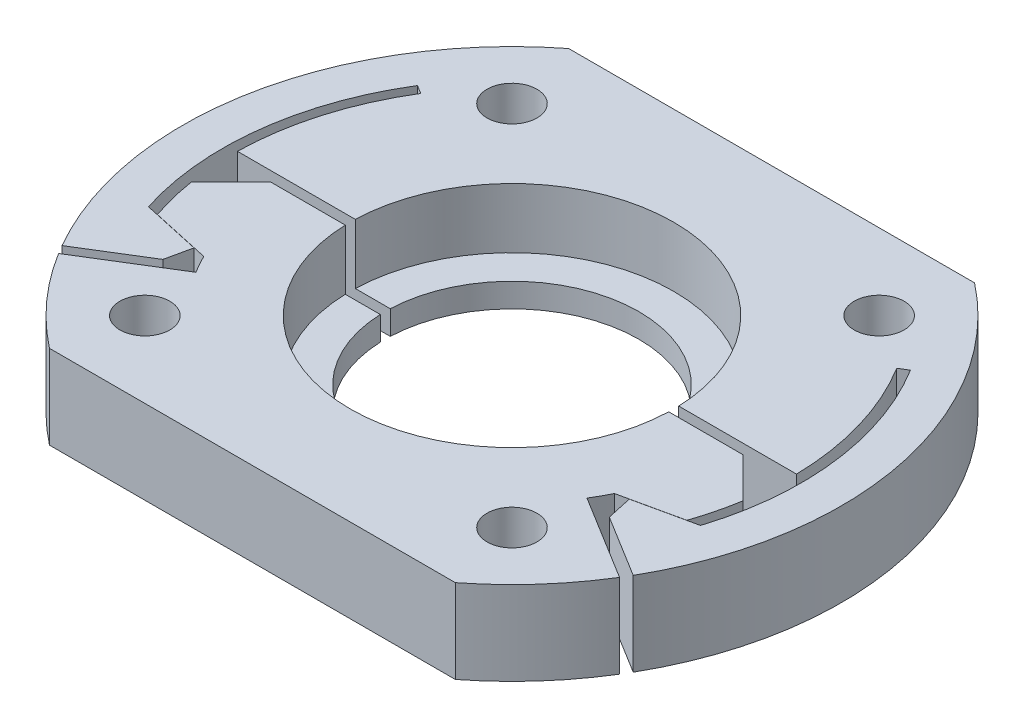
SolidWorks part; units mm, degrees
ref_plane "Front Plane" through (0, 0, 0) normal (0, 0, 1) x (1, 0, 0)
ref_plane "Top Plane" through (0, 0, 0) normal (0, 1, 0) x (1, 0, 0)
ref_plane "Right Plane" through (0, 0, 0) normal (1, 0, 0) x (0, 0, -1)
sketch "Sketch1" plane through (0, 0, 0) normal (0, 0, 1) x (1, 0, 0)
  line L0 (0, 21.7375) -> (0, -20.1262) construction
  line L1 (0, -30.2326) -> (0, 30.2326) construction
  line L2 (0, -18) -> (-11.8744, -18) construction
  line L3 (29.2568, 0) -> (-29.2568, 0) construction
  line L4 (-3, 0) -> (-8, 0)
  line L5 (-8, 0) -> (-8, -3.7)
  line L6 (-8, -3.7) -> (-6, -3.7)
  line L7 (-6, -3.7) -> (-6, -9.7)
  line L8 (-6, -9.7) -> (-8, -9.7)
  line L9 (-8, -9.7) -> (-8, -13)
  line L10 (-8, -13) -> (-3, -13)
  line L11 (-3, -13) -> (-3, 0)
  line L12 (-3, -13) -> (-16.5, -13)
  line L13 (-3, -13) -> (-3, -14.3)
  line L14 (-3, -14.3) -> (-16.5, -14.3)
  line L15 (-8, 0) -> (-3, 0)
  line L16 (-16.5, -13) -> (-16.5, -14.3)
  line L17 (-16.5, -14.3) -> (-8.1, -14.3)
  line L18 (-16.5, -14.3) -> (-16.5, -21)
  line L19 (-16.5, -21) -> (-8.1, -21)
  line L20 (-8.1, -14.3) -> (-8.1, -21)
  line L21 (-16.5, -21) -> (-6.1, -21)
  line L22 (-16.5, -21) -> (-16.5, -23.9)
  line L23 (-16.5, -23.9) -> (-6.1, -23.9)
  line L24 (-6.1, -21) -> (-6.1, -23.9)
  line L25 (-13.1, -10.7008) -> (-13.1, -25.8267) construction
  line L26 (-9.6, -10.9566) -> (-9.6, -25.8267) construction
  line L28 (-8.1, -24) -> (-16.5, -24)
  line L29 (-8.1, -24) -> (-8.1, -27)
  line L30 (-8.1, -27) -> (-16.5, -27)
  line L31 (-16.5, -24) -> (-16.5, -27)
  line L32 (-16.5, -27) -> (-6.35, -27)
  line L33 (-16.5, -27) -> (-16.5, -28.2)
  line L34 (-16.5, -28.2) -> (-6.35, -28.2)
  line L35 (-6.35, -27) -> (-6.35, -28.2)
  line L36 (-16.5, -28.2) -> (-8.1, -28.2)
  line L37 (-16.5, -28.2) -> (-16.5, -29.4)
  line L38 (-16.5, -29.4) -> (-8.1, -29.4)
  line L39 (-8.1, -28.2) -> (-8.1, -29.4)
  dimension "D1" = 12
  dimension "D2" = 16
  dimension "D3" = 6
  dimension "D4" = 3.7
  dimension "D5" = 3.3
  dimension "D6" = 6
  dimension "D7" = 1.3
  dimension "D8" = 33
  dimension "D9" = 0.1
  dimension "D10" = 0.1
  dimension "D11" = 3.7
  dimension "D12" = 3
  dimension "D13" = 5.9
  dimension "D14" = 3.5
  dimension "D15" = 1.5
  dimension "D16" = 16.2
  dimension "D17" = 3
  dimension "D18" = 0.1
  dimension "D19" = 12.7
  dimension "D20" = 1.2
  dimension "D21" = 1.2
revolve "Revolve1" add sketch "Sketch1" angle 360 mid plane about L0 region at (-5.1604, -6.4547, 0) region at (-9.75, -13.65, 0) region at (-12.3, -17.65, 0) region at (-11.3, -22.45, 0)
sketch "Sketch4" plane through (0, -13, 0) normal (0, 1, 0) x (1, 0, 0)
  line L1 (9.1924, -9.1924) -> (-9.1924, -9.1924) construction
  line L2 (9.1924, -9.1924) -> (9.1924, 9.1924) construction
  line L3 (9.1924, 9.1924) -> (-9.1924, 9.1924) construction
  line L4 (-9.1924, -9.1924) -> (-9.1924, 9.1924) construction
  line L5 (9.1924, -9.1924) -> (-9.1924, 9.1924) construction
  line L6 (9.1924, 9.1924) -> (-9.1924, -9.1924) construction
  circle A0 centre (-9.1924, 9.1924) radius 2.25
  circle A1 centre (9.1924, 9.1924) radius 2.25
  circle A2 centre (9.1924, -9.1924) radius 2.25
  circle A3 centre (-9.1924, -9.1924) radius 2.25
  circle A4 centre (-9.1924, -9.1924) radius 1.2
  circle A5 centre (-9.1924, 9.1924) radius 1.2
  circle A6 centre (9.1924, 9.1924) radius 1.2
  circle A7 centre (9.1924, -9.1924) radius 1.2
  point P0 (0, 0)
  dimension "D2" = 2.4
  dimension "D3" = 4.5
  dimension "D1" = 26
extrude "Cut-Extrude2" cut sketch "Sketch4" against normal through all contours A5 | A6 | A7 | A4 region at (-9.1924, -13, 9.1924) region at (-9.1924, -13, -9.1924) region at (9.1924, -13, -9.1924) region at (9.1924, -13, 9.1924)
extrude "Cut-Extrude3" cut sketch "Sketch4<3>" against normal offset from surface (9.4 mm away) 1.5 contours A1 A6 | A2 A7 | A3 A4 | A5 | A0 region at (7.006, -13, -9.1924) region at (7.006, -13, 9.1924) region at (-11.3787, -13, 9.1924) up to face at (-9.1924, -23.9, 10.3924)
sketch "Sketch4<3>" plane through (0, -13, 0) normal (0, 1, 0) x (1, 0, 0) same geometry as "Sketch4"
chamfer "Chamfer1" distance 1 angle 45 1 edges at (0, 0, 3)
sketch "Sketch2" plane through (0, 0, 0) normal (0, 0, 1) x (1, 0, 0)
  line L1 (20.8544, 27.2883) -> (-20.8544, 27.2883)
  line L2 (20.8544, 27.2883) -> (20.8544, -27.2883)
  line L3 (20.8544, -27.2883) -> (-20.8544, -27.2883)
  line L4 (-20.8544, 27.2883) -> (-20.8544, -27.2883)
  line L5 (20.8544, 27.2883) -> (-20.8544, -27.2883) construction
  line L6 (20.8544, -27.2883) -> (-20.8544, 27.2883) construction
  point P0 (0, 0)
extrude "Cut-Extrude1" cut sketch "Sketch2" against normal mid plane 0.1
revolve "Revolve2" add sketch "Sketch1<5>" angle 360 about L0 region at (-12.3, -25.5, 0) region at (-11.425, -27.6, 0) region at (-12.3, -28.8, 0)
sketch "Sketch1<5>" plane through (0, 0, 0) normal (0, 0, 1) x (1, 0, 0) same geometry as "Sketch1"
delete or keep bodies "Body-Delete/Keep 1" type delete bodies bodies 108 109
sketch "Sketch10" plane through (0, -29.4, 0) normal (0, -1, 0) x (1, 0, 0)
  circle A0 centre (-9.1924, 9.1924) radius 1.25
  circle A1 centre (9.1924, 9.1924) radius 1.25
  circle A2 centre (9.1924, -9.1924) radius 1.25
  circle A3 centre (-9.1924, -9.1924) radius 1.25
  dimension "D1" = 2.5
extrude "Cut-Extrude9" cut sketch "Sketch10" against normal through all
sketch "Sketch6" plane through (0, -24, 0) normal (0, 1, 0) x (1, 0, 0)
  line L0 (-13.8219, -4.3823) -> (-10.2761, -5.1625)
  line L1 (0, 0) -> (-12.3424, 7.6102)
  line L2 (-13.8219, -4.3823) -> (-10.9622, -3.4756) construction
  line L3 (-9.7888, -6.0357) -> (-14.0448, -8.6599)
  line L4 (-10.8968, -5.0259) -> (-11.1782, -6.305)
  line L5 (-14.3008, -8.2303) -> (-10.042, -5.6044)
  line L6 (-13.8254, -4.3713) -> (-10.2819, -5.151)
  line L7 (35.7851, -0.25) -> (-35.7851, -0.25)
  line L8 (35.7851, -0.25) -> (35.7851, 0.25)
  line L9 (35.7851, 0.25) -> (-35.7851, 0.25)
  line L10 (-35.7851, -0.25) -> (-35.7851, 0.25)
  line L11 (35.7851, -0.25) -> (-35.7851, 0.25) construction
  line L12 (35.7851, 0.25) -> (-35.7851, -0.25) construction
  line L13 (0, 0.25) -> (0, -0.25)
  line L14 (-11.818, -0.25) -> (-13.818, -2.25)
  circle A0 centre (0, 0) radius 8.1 construction
  circle A1 centre (0, 0) radius 6.35 construction
  circle A2 centre (0, 0) radius 16.5 construction
  circle A3 centre (0, 0) radius 8.1
  circle A4 centre (0, 0) radius 6.35
  circle A5 centre (0, 0) radius 16.5
  circle A6 centre (0, 0) radius 14.5
  circle A7 centre (0, 0) radius 11.5
  circle A8 centre (0, 0) radius 14
  circle A9 centre (0, 0) radius 12
  circle A12 centre (-9.1924, 9.1924) radius 1.25 construction
  circle A13 centre (-9.1924, -9.1924) radius 1.25 construction
  circle M11 centre (0, 0) radius 16.5
  circle M12 centre (0, 0) radius 8.1
  dimension "D1" = 2
  dimension "D2" = 0.5
  dimension "D4" = 0.5
  dimension "D8" = 3
  dimension "D3" = 3
  dimension "D5" = 30
  dimension "D6" = 1
  dimension "D7" = 3
  dimension "D9" = 0.5
  dimension "D10" = 0.5
  dimension "D11" = 0.01
  dimension "D12" = 2
  dimension "D13" = 45
extrude "Cut-Extrude6" cut sketch "Sketch6" against normal blind 10 contours L9 A4 L7 L13 L1 | A8 L1 A6 L9 | A4 L9 L7 M12 | L9 A7 L7 M12 | L9 A9 L7 A7 | A9 L9 A8 L7 | A8 L9 A6 L7 | A8 L7 A6 L6 | A8 L6 A6 L0 | A9 L6 A8 L0 | L6 A9 L0 A7 | L0 A9 L5 A7 | A6 L5 L3 M11 | A8 L5 A6 L3 | A9 L5 A8 L3 | L5 A9 L3 A7 | A9 L7 A8 L14 | A9 L4 L5 | L7 A9 L14 region at (-10.5892, -24, 5.0885) region at (-10.8501, -24, 5.7369) region at (-12.078, -24, 4.7609) region at (-10.4518, -24, 5.4199) region at (-13.5401, -24, 4.4392) region at (-11.1941, -24, 6.6084) region at (-10.1298, -24, 5.9522) region at (-13.9981, -24, 2.3596) region at (-12.2583, -24, 7.2646) region at (-11.9361, -24, 0.3082) region at (-13.2358, -24, 0.9283) region at (-9.7989, -24, 0) region at (-11.7491, -24, 0) region at (-13.3225, -24, 7.9208) region at (-12.9992, -24, 0) region at (-7.2235, -24, 0) region at (-14.2493, -24, 0) region at (-3.2235, -24, 0.0027) region at (-13.514, -24, -3.9598)
sketch "Sketch8" plane through (0, -29.4, 0) normal (0, -1, 0) x (1, 0, 0)
  line L9 (-11.818, 0.25) -> (-8.0961, 0.25)
  line L10 (-11.818, 0.25) -> (-8.0961, 0.25)
  line L11 (-8.0961, -0.25) -> (-13.9978, -0.25)
  line L12 (-8.0961, -0.25) -> (-13.9978, -0.25)
  line L13 (-11.9168, -7.3478) -> (-12.3424, -7.6102)
  line L14 (-11.9168, -7.3478) -> (-12.3424, -7.6102)
  line L15 (-13.8219, 4.3823) -> (-10.8968, 5.0259)
  line L16 (-13.8219, 4.3823) -> (-10.8968, 5.0259)
  line L17 (-11.1782, 6.305) -> (-14.3008, 8.2303)
  line L18 (-11.1782, 6.305) -> (-14.3008, 8.2303)
  line L19 (-14.0448, 8.6599) -> (-9.7888, 6.0357)
  line L20 (-14.0448, 8.6599) -> (-9.7888, 6.0357)
  line L21 (-10.2819, 5.151) -> (-13.2584, 4.4961)
  line L22 (-10.2819, 5.151) -> (-13.2584, 4.4961)
  line L23 (-10.8968, 5.0259) -> (-11.1782, 6.305)
  line L24 (-10.8968, 5.0259) -> (-11.1782, 6.305)
  line L25 (-13.818, 2.25) -> (-11.818, 0.25)
  line L26 (-13.818, 2.25) -> (-11.818, 0.25)
  arc A6 (-13.2584, 4.4961) -> (-13.818, 2.25) centre (0, 0) ccw
  arc A7 (-13.2584, 4.4961) -> (-13.818, 2.25) centre (0, 0) ccw
  arc A8 (-8.0961, -0.25) -> (-8.0961, 0.25) centre (0, 0) ccw
  arc A9 (-8.0961, -0.25) -> (-8.0961, 0.25) centre (0, 0) ccw
  arc A10 (-13.9978, -0.25) -> (-11.9168, -7.3478) centre (0, 0) ccw
  arc A11 (-13.9978, -0.25) -> (-11.9168, -7.3478) centre (0, 0) ccw
  arc A12 (-14.3008, 8.2303) -> (-14.0448, 8.6599) centre (0, 0) ccw
  arc A13 (-13.8219, 4.3823) -> (-12.3424, -7.6102) centre (0, 0) ccw
  arc A14 (-13.8219, 4.3823) -> (-12.3424, -7.6102) centre (0, 0) ccw
  arc A15 (-9.7888, 6.0357) -> (-10.2819, 5.151) centre (0, 0) ccw
  arc A16 (-9.7888, 6.0357) -> (-10.2819, 5.151) centre (0, 0) ccw
  arc A19 (-14.3008, 8.2303) -> (-14.0448, 8.6599) centre (0, 0) ccw
  dimension "D1" = 0
extrude "Cut-Extrude7" cut sketch "Sketch8" against normal up to surface (1.2 mm away) up to face at (0.0022, -28.2, 0)
mirror "Mirror2" about plane through (0, 0, 0) normal (1, 0, 0) of "Cut-Extrude6"
sketch "Sketch11" plane through (0, -24, 0) normal (0, 1, 0) x (1, 0, 0)
  line L1 (30, -13) -> (-30, -13)
  line L2 (30, -13) -> (30, 13)
  line L3 (30, 13) -> (-30, 13)
  line L4 (-30, -13) -> (-30, 13)
  line L5 (30, -13) -> (-30, 13) construction
  line L6 (30, 13) -> (-30, -13) construction
  point P0 (0, 0)
  dimension "D1" = 26
  dimension "D2" = 60
extrude "Cut-Extrude10" cut sketch "Sketch11" against normal through all flip side to cut
